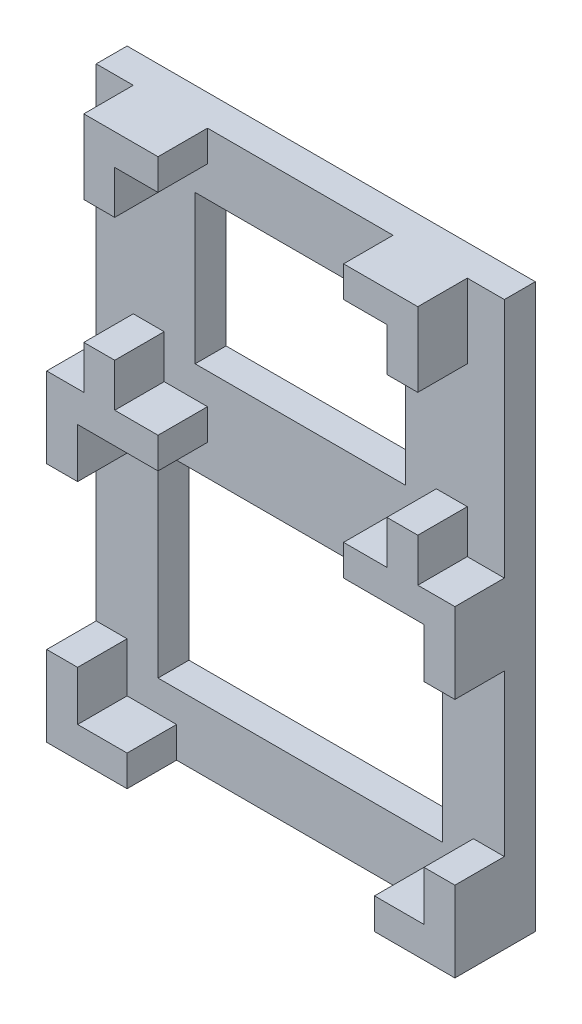
SolidWorks part; units mm, degrees
ref_plane "Front Plane" through (0, 0, 0) normal (0, 0, 1) x (1, 0, 0)
ref_plane "Top Plane" through (0, 0, 0) normal (0, 1, 0) x (1, 0, 0)
ref_plane "Right Plane" through (0, 0, 0) normal (1, 0, 0) x (0, 0, -1)
sketch "Sketch1" plane through (0, 0, 0) normal (0, 0, 1) x (1, 0, 0)
  line L0 (33, 52) -> (33, 47) construction
  line L1 (0, 0) -> (66, 0)
  line L2 (0, 0) -> (0, 91)
  line L3 (0, 91) -> (66, 91)
  line L4 (66, 0) -> (66, 91)
  line L5 (0, 0) -> (66, 0)
  line L6 (0, 0) -> (0, 42)
  line L8 (66, 0) -> (66, 42)
  line L9 (11, 52) -> (55, 52)
  line L12 (61, 5) -> (5, 5)
  line L13 (61, 5) -> (61, 47)
  line L14 (61, 47) -> (5, 47)
  line L15 (5, 5) -> (5, 47)
  line L17 (55, 52) -> (55, 86)
  line L19 (11, 69) -> (0, 69) construction
  line L24 (55, 52) -> (11, 52)
  line L25 (55, 52) -> (55, 86)
  line L26 (55, 86) -> (11, 86)
  line L27 (11, 52) -> (11, 86)
  line L28 (33, 5) -> (33, 0) construction
  line L29 (5, 26) -> (0, 26) construction
  line L30 (33, 86) -> (33, 91) construction
  line L31 (11, 52) -> (18, 52)
  line L32 (13, 0) -> (0, 0)
  line L33 (13, 0) -> (13, 5)
  line L34 (13, 5) -> (5, 5)
  line L35 (0, 0) -> (0, 5)
  line L36 (0, 0) -> (5, 0)
  line L37 (0, 0) -> (0, 13)
  line L38 (0, 13) -> (5, 13)
  line L39 (5, 5) -> (5, 13)
  line L40 (66, 0) -> (53, 0)
  line L41 (66, 0) -> (66, 5)
  line L42 (61, 5) -> (53, 5)
  line L43 (53, 0) -> (53, 5)
  line L44 (66, 0) -> (61, 0)
  line L45 (66, 0) -> (66, 13)
  line L46 (66, 13) -> (61, 13)
  line L47 (61, 5) -> (61, 13)
  line L49 (5, 47) -> (5, 39)
  line L50 (5, 39) -> (0, 39)
  line L51 (0, 47) -> (0, 39)
  line L52 (0, 52) -> (6, 52)
  line L53 (0, 52) -> (0, 47)
  line L54 (5, 47) -> (18, 47)
  line L55 (18, 52) -> (18, 47)
  line L57 (61, 47) -> (61, 39)
  line L58 (61, 39) -> (66, 39)
  line L59 (66, 47) -> (66, 39)
  line L60 (61, 47) -> (48, 47)
  line L61 (66, 47) -> (66, 52)
  line L62 (66, 52) -> (60, 52)
  line L63 (48, 47) -> (48, 52)
  line L65 (11, 52) -> (11, 59)
  line L66 (11, 59) -> (6, 59)
  line L67 (6, 52) -> (6, 59)
  line L68 (55, 52) -> (48, 52)
  line L70 (55, 52) -> (55, 59)
  line L71 (55, 59) -> (60, 59)
  line L72 (60, 52) -> (60, 59)
  line L73 (33, 81) -> (33, 86) construction
  line L74 (11, 86) -> (18, 86)
  line L76 (11, 91) -> (18, 91)
  line L77 (18, 86) -> (18, 91)
  line L78 (55, 86) -> (48, 86)
  line L80 (55, 91) -> (48, 91)
  line L81 (48, 86) -> (48, 91)
  line L82 (55, 91) -> (60, 91)
  line L83 (55, 86) -> (55, 79)
  line L84 (55, 79) -> (60, 79)
  line L85 (60, 91) -> (60, 79)
  line L86 (11, 91) -> (6, 91)
  line L87 (11, 86) -> (11, 79)
  line L88 (11, 79) -> (6, 79)
  line L89 (6, 91) -> (6, 79)
  line L90 (55, 52) -> (11, 52)
  line L91 (55, 52) -> (55, 57)
  line L92 (50, 57) -> (16, 57)
  line L93 (11, 52) -> (11, 57)
  line L94 (55, 52) -> (50, 52)
  line L95 (55, 52) -> (55, 86)
  line L96 (55, 86) -> (50, 86)
  line L97 (50, 57) -> (50, 81)
  line L98 (55, 86) -> (11, 86)
  line L99 (55, 86) -> (55, 81)
  line L100 (50, 81) -> (16, 81)
  line L101 (11, 86) -> (11, 81)
  line L102 (11, 86) -> (16, 86)
  line L103 (11, 86) -> (11, 52)
  line L104 (11, 52) -> (16, 52)
  line L105 (16, 81) -> (16, 57)
  line L106 (16, 69) -> (11, 69) construction
  line L107 (33, 5) -> (33, 10) construction
  line L108 (33, 47) -> (33, 42) construction
  line L109 (5, 26) -> (10, 26) construction
  line L110 (61, 26) -> (56, 26) construction
  dimension "D1" = 66
  dimension "D2" = 91
  dimension "D3" = 42
  dimension "D4" = 5
  dimension "D5" = 5
  dimension "D6" = 5
  dimension "D7" = 42
  dimension "D8" = 11
  dimension "D9" = 5
  dimension "D10" = 13
  dimension "D11" = 13
  dimension "D12" = 13
  dimension "D13" = 13
  dimension "D14" = 8
  dimension "D15" = 18
  dimension "D16" = 13
  dimension "D17" = 11
  dimension "D18" = 18
  dimension "D19" = 13
  dimension "D20" = 7
  dimension "D21" = 5
  dimension "D22" = 5
  dimension "D23" = 7
  dimension "D24" = 5
  dimension "D25" = 12
  dimension "D26" = 12
  dimension "D27" = 5
  dimension "D28" = 7
  dimension "D29" = 5
  dimension "D30" = 7
  dimension "D31" = 5
  dimension "D32" = 5
  dimension "D33" = 5
  dimension "D34" = 5
  dimension "D35" = 5
  dimension "D36" = 5
  dimension "D37" = 5
  dimension "D38" = 5
  dimension "D39" = 5
  dimension "D40" = 5
  dimension "D41" = 5
extrude "Boss-Extrude1" add sketch "Sketch1" along normal blind 5 contours L27 L9 L90 L24 L17 L70 L25 L95 L26 L78 L98 L87 L65 L105 L100 L97 L92 | L89 L3 L2 L52 L67 L66 L27 L88 | L26 L81 L3 L77 | L3 L85 L84 L25 L71 L72 L62 L4 | L58 L13 L46 L4 | L14 L63 L24 L55 | L15 L50 L2 L38 | L5 L43 L12 L33 region at (33, 2.5, 0) region at (2.5, 26, 0) region at (63.5, 26, 0) region at (4.6467, 70.7515, 0) region at (33, 49.5, 0) region at (17, 52.5561, 0) region at (33, 88.5, 0) region at (61.3533, 70.7515, 0)
extrude "Boss-Extrude2" add sketch "Sketch1<3>" along normal blind 13 contours L67 L52 L2 L6 L50 L15 L14 L55 L90 L9 L27 L65 L66 | L3 L89 L88 L27 L87 L98 L26 L77 | L85 L3 L81 L78 L26 L95 L17 L84 | L62 L72 L71 L70 L17 L90 L9 L63 L14 L13 L58 L8 L4 | L8 L46 L13 L12 L43 L1 L40 L4 | L38 L6 L2 L1 L32 L33 L12 L15 region at (4.9762, 4.9762, 0) region at (61.0238, 4.9762, 0) region at (7.3182, 49.197, 0) region at (58.6818, 49.197, 0) region at (10.7105, 86.2895, 0) region at (55.2895, 86.2895, 0)
sketch "Sketch1<3>" plane through (0, 0, 0) normal (0, 0, 1) x (1, 0, 0) same geometry as "Sketch1"
sketch "Sketch2" plane through (0, 0, 5) normal (0, 0, 1) x (1, 0, 0)
  line L0 (18, 47) -> (5, 47) construction
  line L1 (5, 5) -> (10, 5)
  line L2 (5, 5) -> (5, 47)
  line L3 (5, 47) -> (10, 47)
  line L4 (10, 10) -> (10, 42)
  line L5 (61, 39) -> (61, 47) construction
  line L6 (5, 47) -> (61, 47)
  line L7 (5, 47) -> (5, 42)
  line L8 (10, 42) -> (56, 42)
  line L9 (61, 47) -> (61, 42)
  line L10 (33, 42) -> (33, 47) construction
  line L11 (61, 5) -> (56, 5)
  line L12 (61, 5) -> (61, 47)
  line L13 (61, 47) -> (56, 47)
  line L14 (56, 10) -> (56, 42)
  line L15 (5, 5) -> (61, 5)
  line L16 (5, 5) -> (5, 10)
  line L17 (10, 10) -> (56, 10)
  line L18 (61, 5) -> (61, 10)
  line L19 (10, 26) -> (5, 26) construction
  line M9 (53, 5) -> (13, 5)
  dimension "D1" = 5
  dimension "D2" = 5
  dimension "D3" = 5
  dimension "D4" = 5
  dimension "D5" = 5
  dimension "D6" = 5
extrude "Boss-Extrude6" add sketch "Sketch2" against normal blind 5 contours L1 L15 L11 L12 L9 L6 L3 L2 L17 L4 L8 L14 M9 region at (5.7, 7.5, 5)
